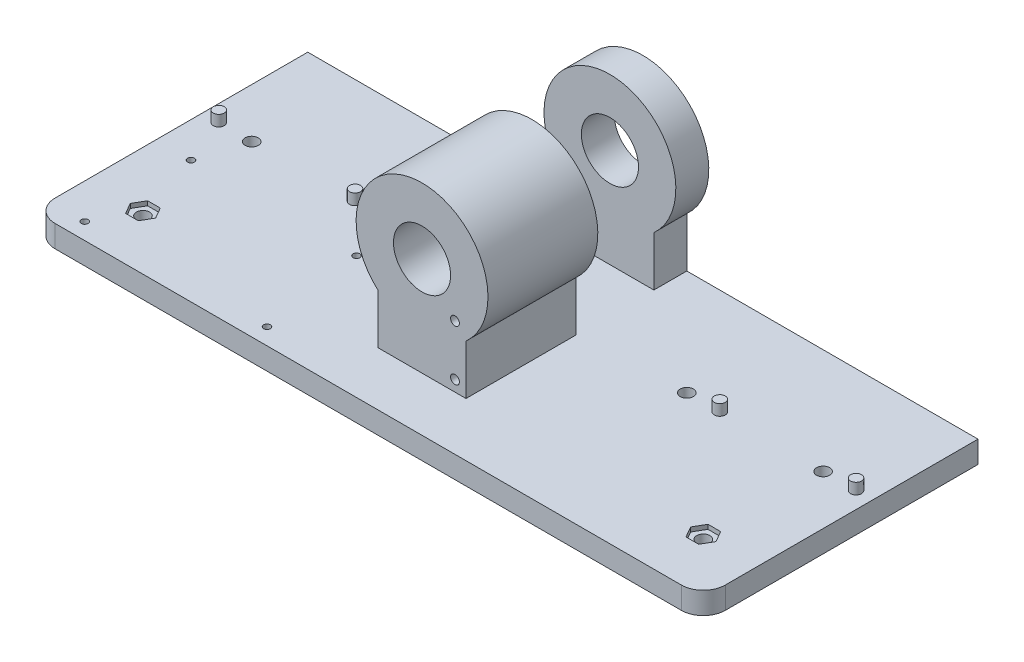
SolidWorks part; units mm, degrees
ref_plane "Front Plane" through (0, 0, 0) normal (0, 0, 1) x (1, 0, 0)
ref_plane "Top Plane" through (0, 0, 0) normal (0, 1, 0) x (1, 0, 0)
ref_plane "Right Plane" through (0, 0, 0) normal (1, 0, 0) x (0, 0, -1)
sketch "Sketch1" plane through (0, 0, 0) normal (0, 1, 0) x (1, 0, 0)
  line L0 (152.5, 125) -> (152.5, 0) construction
  line L1 (0, 0) -> (305, 0)
  line L2 (0, 0) -> (0, 125)
  line L3 (0, 125) -> (305, 125)
  line L4 (305, 0) -> (305, 125)
  line L5 (25, 100) -> (280, 100) construction
  line L6 (280, 25) -> (280, 100) construction
  line L7 (25, 25) -> (280, 25) construction
  line L8 (25, 25) -> (25, 100) construction
  line L9 (152.5, 62.5) -> (25, 62.5) construction
  line L10 (30.7735, 100) -> (27.8868, 105) construction
  line L11 (27.8868, 105) -> (22.1132, 105) construction
  line L12 (22.1132, 105) -> (19.2265, 100) construction
  line L13 (19.2265, 100) -> (22.1132, 95) construction
  line L14 (22.1132, 95) -> (27.8868, 95) construction
  line L15 (27.8868, 95) -> (30.7735, 100) construction
  line L16 (27.8868, 30) -> (30.7735, 25) construction
  line L17 (22.1132, 30) -> (27.8868, 30) construction
  line L18 (19.2265, 25) -> (22.1132, 30) construction
  line L19 (22.1132, 20) -> (19.2265, 25) construction
  line L20 (27.8868, 20) -> (22.1132, 20) construction
  line L21 (30.7735, 25) -> (27.8868, 20) construction
  line L22 (282.8868, 30) -> (277.1132, 30) construction
  line L23 (285.7735, 25) -> (282.8868, 30) construction
  line L24 (282.8868, 20) -> (285.7735, 25) construction
  line L25 (277.1132, 20) -> (282.8868, 20) construction
  line L26 (274.2265, 25) -> (277.1132, 20) construction
  line L27 (277.1132, 30) -> (274.2265, 25) construction
  line L28 (277.1132, 95) -> (274.2265, 100) construction
  line L29 (282.8868, 95) -> (277.1132, 95) construction
  line L30 (285.7735, 100) -> (282.8868, 95) construction
  line L31 (282.8868, 105) -> (285.7735, 100) construction
  line L32 (277.1132, 105) -> (282.8868, 105) construction
  line L33 (274.2265, 100) -> (277.1132, 105) construction
  line L34 (172.5, 75) -> (172.5, 125) construction
  line L35 (132.5, 0) -> (172.5, 0) construction
  line L36 (132.5, 0) -> (132.5, 125) construction
  line L37 (132.5, 125) -> (172.5, 125) construction
  line L38 (172.5, 0) -> (172.5, 125) construction
  line L40 (132.5, 75) -> (132.5, 25) construction
  line L41 (132.5, 25) -> (172.5, 25) construction
  line L42 (172.5, 75) -> (172.5, 25) construction
  line L50 (305, 14.5) -> (253.3, 14.5) construction
  line L51 (0, 84.5) -> (15, 69.5) construction
  line L54 (0, 125) -> (108, 125) construction
  line L55 (0, 125) -> (0, 84.5) construction
  line L56 (0, 84.5) -> (108, 84.5) construction
  line L57 (108, 125) -> (108, 84.5) construction
  line L58 (15, 69.5) -> (15, 84.5) construction
  line L59 (30, 84.5) -> (0, 84.5) construction
  line L60 (30, 84.5) -> (30, 69.5) construction
  line L61 (30, 69.5) -> (0, 69.5) construction
  line L62 (0, 84.5) -> (0, 69.5) construction
  line L63 (92, 84.5) -> (92, 69.5) construction
  line L64 (62, 0) -> (62, 125) construction
  line L65 (253.3, 14.5) -> (253.3, 0) construction
  line L67 (253.3, 14.5) -> (280.2, 14.5) construction
  circle A1 centre (25, 100) radius 5 construction
  circle A3 centre (280, 25) radius 3
  circle A4 centre (25, 25) radius 3
  circle A10 centre (7.5, 77) radius 3 construction
  circle A11 centre (22.5, 77) radius 3
  circle A12 centre (69.5, 77) radius 3 construction
  circle A13 centre (84.5, 77) radius 3
  circle A14 centre (220.5, 77) radius 3
  circle A15 centre (235.5, 77) radius 3 construction
  circle A16 centre (282.5, 77) radius 3
  circle A17 centre (297.5, 77) radius 3 construction
  point P50 (0, 0)
  point P85 (280, 46.7517)
  dimension "D3" = 6
  dimension "D1" = 305
  dimension "D2" = 125
  dimension "D5" = 10
  dimension "D6" = 40
  dimension "D7" = 40.5
  dimension "D9" = 108
  dimension "D10" = 15
  dimension "D11" = 30
  dimension "D15" = 62
  dimension "D18" = 51.7
  dimension "D19" = 14.5
  dimension "D20" = 26.9
  dimension "D4" = 25
  dimension "D14" = 2
extrude "Boss-Extrude1" add sketch "Sketch1" along normal blind 10
sketch "Sketch7" plane through (0, 10, 0) normal (0, 1, 0) x (1, 0, 0)
  line L0 (0, 0) -> (305, 0) construction
  line L1 (132.5, 24.5) -> (172.5, 24.5)
  line L2 (132.5, 24.5) -> (132.5, 74.5)
  line L3 (132.5, 74.5) -> (172.5, 74.5)
  line L4 (172.5, 24.5) -> (172.5, 74.5)
  line L5 (152.5, 0) -> (152.5, 125) construction
  line L6 (305, 125) -> (0, 125) construction
  line L18 (132.5, 110) -> (172.5, 110)
  line L19 (132.5, 110) -> (132.5, 125)
  line L20 (132.5, 125) -> (172.5, 125)
  line L21 (172.5, 110) -> (172.5, 125)
  point P11 (152.5, 74.5)
  point P20 (152.5, 110)
  dimension "D1" = 40
  dimension "D2" = 50
  dimension "D4" = 15
  dimension "D3" = 35.5
extrude "Boss-Extrude2" add sketch "Sketch7" along normal blind 22.6393
sketch "Sketch11" plane through (0, 0, -24.5) normal (0, 0, 1) x (1, 0, 0)
  circle A0 centre (152.5, 55) radius 30
  circle A1 centre (152.5, 55) radius 13
  dimension "D1" = 60
  dimension "D2" = 26
extrude "Boss-Extrude3" add sketch "Sketch11" against normal up to surface (100.5 mm away) up to face at (152.5, 13.1598, -125)
ref_plane "Plane1" through (0, 0, -62.5) normal (0, 0, 1) x (1, 0, 0)
sketch "Sketch12" plane through (305, 0, 0) normal (1, 0, 0) x (0, 0, -1)
  line L0 (125, 85) -> (24.5, 85) construction
  line L1 (74.5, 10) -> (110, 10)
  line L2 (74.5, 10) -> (74.5, 85)
  line L3 (74.5, 85) -> (110, 85)
  line L4 (110, 10) -> (110, 85)
  line L6 (110, 32.6393) -> (110, 10) construction
extrude "Cut-Extrude2" cut sketch "Sketch12" against normal through all
sketch "Sketch6" plane through (0, 10, 0) normal (0, 1, 0) x (1, 0, 0)
  line L0 (152.5, 125) -> (152.5, 0) construction
  line L8 (0, 0) -> (305, 0) construction
  line L9 (152.5, 62.5) -> (0, 62.5) construction
  line L10 (0, 125) -> (0, 0) construction
  line L29 (27.8868, 30) -> (30.7735, 25)
  line L30 (274.2265, 25) -> (277.1132, 20)
  line L31 (277.1132, 20) -> (282.8868, 20)
  line L32 (282.8868, 20) -> (285.7735, 25)
  line L33 (285.7735, 25) -> (282.8868, 30)
  line L34 (282.8868, 30) -> (277.1132, 30)
  line L35 (277.1132, 30) -> (274.2265, 25)
  line L36 (22.1132, 30) -> (27.8868, 30)
  line L37 (19.2265, 25) -> (22.1132, 30)
  line L38 (22.1132, 20) -> (19.2265, 25)
  line L39 (27.8868, 20) -> (22.1132, 20)
  line L40 (30.7735, 25) -> (27.8868, 20)
  circle A0 centre (280, 25) radius 5 construction
  dimension "D1" = 10
extrude "Cut-Extrude1" cut sketch "Sketch6" against normal blind 2
sketch "Sketch15" plane through (0, 10, 0) normal (0, 1, 0) x (1, 0, 0)
  line L0 (69.5, 77) -> (7.5, 77) construction
  line L1 (38.5, 77) -> (38.5, 84.5) construction
  line L2 (0, 84.5) -> (108, 84.5) construction
  line L3 (152.5, 125) -> (152.5, 0) construction
  circle A1 centre (69.5, 77) radius 2.5
  circle A2 centre (7.5, 77) radius 2.5
  circle A3 centre (7.5, 77) radius 2.5
  circle A4 centre (235.5, 77) radius 2.5
  circle A5 centre (297.5, 77) radius 2.5
  dimension "D1" = 0.5
extrude "Boss-Extrude5" add sketch "Sketch15" along normal blind 5
sketch "Sketch16" plane through (0, 10, 0) normal (0, 1, 0) x (1, 0, 0)
  line L0 (0, 0) -> (305, 0) construction
  line L1 (0, 125) -> (0, 0) construction
  circle A0 centre (16, 7.5) radius 1.55
  circle A1 centre (98.95, 7.5) radius 1.55
  circle A2 centre (16, 55.866) radius 1.55
  circle A3 centre (91.33, 55.866) radius 1.55
  dimension "D1" = 3.1
  dimension "D2" = 7.5
  dimension "D3" = 82.95
  dimension "D4" = 16
  dimension "D5" = 48.366
  dimension "D6" = 75.33
extrude "Cut-Extrude3" cut sketch "Sketch16" against normal through all
chamfer "Chamfer1" distance 3.3 angle 45 4 edges at (282.5, 0, -74) (220.5, 0, -74) (84.5, 0, -80) (22.5, 0, -80)
fillet "Fillet3" radius 10 2 edges at (305, 5, 0) (0, 5, 0)
fillet "Fillet2" [suppressed] radius 0.5
chamfer "Chamfer2" distance 1.65 4 edges at (98.95, 0, -5.95) (91.33, 0, -54.316) (16, 0, -5.95) (16, 0, -54.316)
sketch "Sketch17" plane through (0, 0, -24.5) normal (0, 0, 1) x (1, 0, 0)
  line L0 (167.5, 15) -> (167.5, 38.11) construction
  line L2 (172.5, 10) -> (167.5, 15) construction
  circle A0 centre (167.5, 15) radius 2
  circle A1 centre (167.5, 38.11) radius 2
  dimension "D2" = 4
  dimension "D1" = 23.11
  dimension "D3" = 5
  dimension "D4" = 5
extrude "Cut-Extrude4" cut sketch "Sketch17" against normal up to next
equation "\"joint_width\"=4"
equation "\"short_base_length\"=12.5"
equation "\"D2@Sketch1\"=\"short_base_length\""
equation "\"outer_diam_main_joint\"=6"
equation "\"D1@Sketch11\"=\"outer_diam_main_joint\""
equation "\"D1@Sketch7\"=\"outer_diam_main_joint\"-2"
equation "\"D1@Boss-Extrude2\"=(\"outer_diam_main_joint\"/2)+1.5cm-sqr((\"outer_diam_main_joint\"/2)^2-((\"outer_diam_main_joint\"-2)/2)^2)"
equation "\"D6@Sketch1\"=\"outer_diam_main_joint\"-2"
equation "\"pulleyside\"=1.5"
